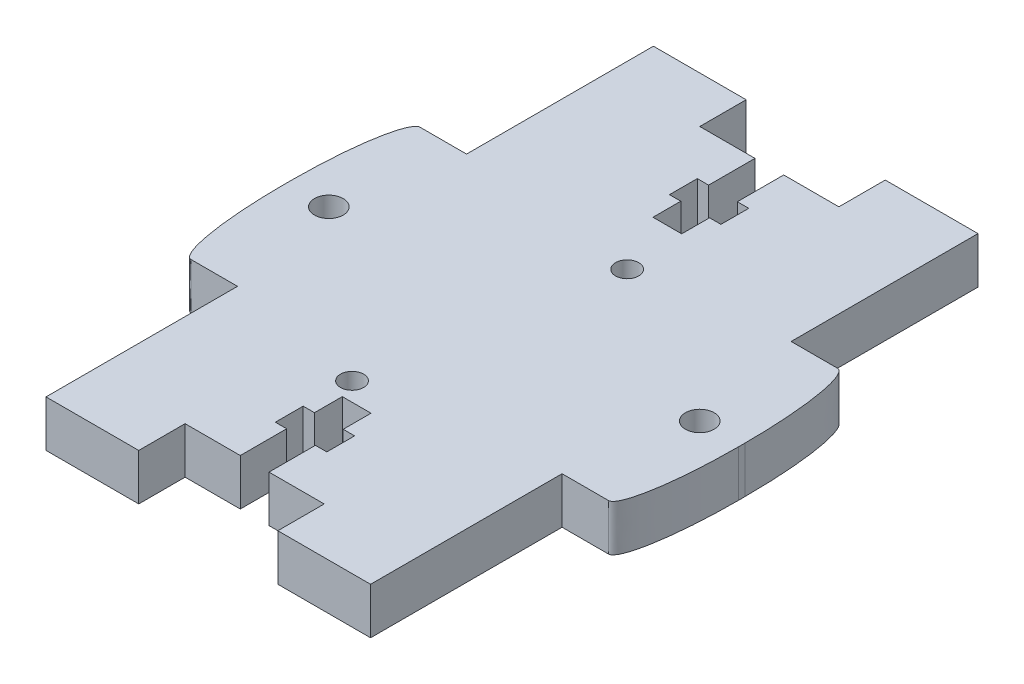
SolidWorks part; units mm, degrees
ref_plane "Plan de face" through (0, 0, 0) normal (0, 0, 1) x (1, 0, 0)
ref_plane "Plan de dessus" through (0, 0, 0) normal (0, 1, 0) x (1, 0, 0)
ref_plane "Plan de droite" through (0, 0, 0) normal (1, 0, 0) x (0, 0, -1)
ref_plane "Plan1" through (0, -5, 0) normal (0, -1, 0) x (1, 0, 0)
sketch "Esquisse1" plane through (0, -5, 0) normal (0, -1, 0) x (1, 0, 0)
  line L0 (17.5, 13.55) -> (17.5, 22.5)
  line L1 (17.5, 22.5) -> (-17.5, 22.5)
  line L2 (-17.5, 22.5) -> (-17.5, 13.55)
  line L3 (-17.5, 12.35) -> (-19.5485, 12.35)
  line L4 (-19.5485, 12.35) -> (-22.1586, 14.9601)
  line L5 (-22.5, 14.8186) -> (-22.5, -14.8186)
  line L6 (-22.1586, -14.9601) -> (-19.5485, -12.35)
  line L7 (-19.5485, -12.35) -> (-17.5, -12.35)
  line L8 (-17.5, -13.55) -> (-17.5, -30)
  line L9 (-17.5, -30) -> (17.5, -30)
  line L10 (17.5, -30) -> (17.5, -13.55)
  line L11 (17.5, -12.35) -> (19.5485, -12.35)
  line L12 (19.5485, -12.35) -> (22.1586, -14.9601)
  line L13 (22.5, -14.8186) -> (22.5, 14.8186)
  line L14 (22.1586, 14.9601) -> (19.5485, 12.35)
  line L15 (19.5485, 12.35) -> (17.5, 12.35)
  arc A0 (-17.5, 13.55) -> (-17.5, 12.35) centre (-17.5, 12.95) cw
  arc A1 (-22.1586, 14.9601) -> (-22.5, 14.8186) centre (-22.3, 14.8186) ccw
  arc A2 (-22.5, -14.8186) -> (-22.1586, -14.9601) centre (-22.3, -14.8186) ccw
  arc A3 (-17.5, -12.35) -> (-17.5, -13.55) centre (-17.5, -12.95) cw
  arc A4 (17.5, -13.55) -> (17.5, -12.35) centre (17.5, -12.95) cw
  arc A5 (22.1586, -14.9601) -> (22.5, -14.8186) centre (22.3, -14.8186) ccw
  arc A6 (22.5, 14.8186) -> (22.1586, 14.9601) centre (22.3, 14.8186) ccw
  arc A7 (17.5, 12.35) -> (17.5, 13.55) centre (17.5, 12.95) cw
extrude "Boss.-Extru.1" add sketch "Esquisse1" against normal blind 5
sketch "Esquisse2" plane through (0, 0, 22.5) normal (0, 0, 1) x (1, 0, 0)
  line L0 (7.95, 0) -> (17.5, 0)
  line L1 (17.5, 0) -> (17.5, -5)
  line L2 (17.5, -5) -> (5, -5)
  line L3 (5, -5) -> (5, -2.95)
  line L4 (5, -2.95) -> (7.95, 0)
extrude "Boss.-Extru.2" add sketch "Esquisse2" along normal blind 8
sketch "Esquisse3" plane through (0, 0, 22.5) normal (0, 0, 1) x (1, 0, 0)
  line L0 (-7.95, 0) -> (-5, -2.95)
  line L1 (-5, -2.95) -> (-5, -5)
  line L2 (-5, -5) -> (-17.5, -5)
  line L3 (-17.5, -5) -> (-17.5, 0)
  line L4 (-17.5, 0) -> (-7.95, 0)
extrude "Boss.-Extru.3" add sketch "Esquisse3" along normal blind 8
fillet "Congé1" radius 1.6 6 edges at (-19.5485, -2.5, 12.35) (19.5485, -2.5, -12.35) (-19.5485, -2.5, -12.35) (5, -2.95, 26.5) (19.5485, -2.5, 12.35) (-5, -2.95, 26.5) tangent propagation no
sketch "Esquisse8" plane through (0, 0, 0) normal (0, 1, 0) x (1, 0, 0)
  line L0 (-17.5, 30) -> (17.5, 30) construction
  line L1 (7.95, -30.5) -> (-7.95, -30.5)
  line L2 (7.95, -30.5) -> (7.95, -22.5)
  line L3 (7.95, -22.5) -> (-7.95, -22.5)
  line L4 (-7.95, -30.5) -> (-7.95, -22.5)
  line L5 (-5.6722, -16.5859) -> (-12.1608, -16.5859)
  line L6 (-5.6722, -16.5859) -> (-5.6722, -5.1949)
  line L7 (-5.6722, -5.1949) -> (-12.1608, -5.1949)
  line L8 (-12.1608, -16.5859) -> (-12.1608, -5.1949)
  line L9 (5.142, 7.638) -> (-5.6722, 7.638)
  line L10 (5.142, 7.638) -> (5.142, 30)
  line L11 (5.142, 30) -> (-5.6722, 30)
  line L12 (-5.6722, 7.638) -> (-5.6722, 30)
  line L13 (17.5, -13.55) -> (17.5, -30.5) construction
  line L14 (17.5, -16.5859) -> (15.5476, -16.5859)
  line L15 (17.5, -16.5859) -> (17.5, 15.4001)
  line L16 (17.5, 15.4001) -> (15.5476, 15.4001)
  line L17 (15.5476, -16.5859) -> (15.5476, 15.4001)
  line L18 (-17.5, -30.5) -> (-17.5, -13.55) construction
  line L19 (-17.5, -15.9862) -> (-14.5166, -15.9862)
  line L20 (-17.5, -15.9862) -> (-17.5, 14.9403)
  line L21 (-17.5, 14.9403) -> (-14.5166, 14.9403)
  line L22 (-14.5166, -15.9862) -> (-14.5166, 14.9403)
  line L23 (17.5, 12.35) -> (18.8858, 12.35) construction
  line L24 (-17.5, -12.35) -> (-24.5, -12.35)
  line L25 (-17.5, -12.35) -> (-17.5, 12.35)
  line L26 (-17.5, 12.35) -> (-24.5, 12.35)
  line L27 (-24.5, -12.35) -> (-24.5, 12.35)
  line L28 (17.5, -12.35) -> (24.5, -12.35)
  line L29 (17.5, -12.35) -> (17.5, 12.35)
  line L30 (17.5, 12.35) -> (24.5, 12.35)
  line L31 (24.5, -12.35) -> (24.5, 12.35)
  line L32 (-18.8858, 12.35) -> (-17.5, 12.35) construction
  line L33 (-22.5, -14.8186) -> (-22.5, 14.8186) construction
  line L34 (22.5, 14.8186) -> (22.5, -14.8186) construction
  arc M5 (17.5, -13.55) -> (17.5, -12.35) centre (17.5, -12.95) cw
  line M10 (22.5, -14.8186) -> (22.5, 14.8186)
  arc M15 (17.5, 12.35) -> (17.5, 13.55) centre (17.5, 12.95) cw
  arc M19 (-17.5, 13.55) -> (-17.5, 12.35) centre (-17.5, 12.95) cw
  line M24 (-22.5, 14.8186) -> (-22.5, -14.8186)
  arc M29 (-17.5, -12.35) -> (-17.5, -13.55) centre (-17.5, -12.95) cw
  line M32 (-7.95, -30.5) -> (-7.95, -22.5)
  line M33 (-7.95, -22.5) -> (7.95, -22.5)
  line M34 (7.95, -22.5) -> (7.95, -30.5)
  dimension "D1" = 0
  dimension "D2" = 0
  dimension "D3" = 2
  dimension "D4" = 2
extrude "Boss.-Extru.4" add sketch "Esquisse8" against normal blind 5 contours L28 L31 L30 M10 | L15 M5 | L15 M15 | L1 M34 M33 M32 | L20 M29 | L27 L24 L26 M24 | L20 M19 region at (0, 0, 26.5) region at (17.2454, 0, 12.95) region at (17.2454, 0, -12.95) region at (23.5, 0, 0) region at (-17.2454, 0, 12.95) region at (-17.2454, 0, -12.95) region at (-23.5, 0, 0)
sketch "Esquisse9" plane through (0, 0, 0) normal (0, 1, 0) x (1, 0, 0)
  line L0 (18.8858, -12.35) -> (17.5, -12.35) construction
  line L1 (18.1929, -12.35) -> (26.3546, -12.35)
  line L2 (18.1929, -12.35) -> (18.1929, -16.2736)
  line L3 (18.1929, -16.2736) -> (26.3546, -16.2736)
  line L4 (26.3546, -12.35) -> (26.3546, -16.2736)
  line L5 (17.5, 12.35) -> (18.8858, 12.35) construction
  line L6 (18.8858, 12.35) -> (24.8026, 12.35)
  line L7 (18.8858, 12.35) -> (18.8858, 17.5845)
  line L8 (18.8858, 17.5845) -> (24.8026, 17.5845)
  line L9 (24.8026, 12.35) -> (24.8026, 17.5845)
  line L10 (-18.8858, 12.35) -> (-17.5, 12.35) construction
  line L11 (-18.1929, 12.35) -> (-25.3236, 12.35)
  line L12 (-18.1929, 12.35) -> (-18.1929, 16.4348)
  line L13 (-18.1929, 16.4348) -> (-25.3236, 16.4348)
  line L14 (-25.3236, 12.35) -> (-25.3236, 16.4348)
  line L15 (-17.5, -12.35) -> (-18.8858, -12.35) construction
  line L16 (-18.1929, -12.35) -> (-23.1392, -12.35)
  line L17 (-18.1929, -12.35) -> (-18.1929, -15.4688)
  line L18 (-18.1929, -15.4688) -> (-23.1392, -15.4688)
  line L19 (-23.1392, -12.35) -> (-23.1392, -15.4688)
  line L20 (-17.5, -30.5) -> (-17.5, -12.35) construction
  line L21 (17.5, -30.5) -> (-17.5, -30.5)
  line L22 (17.5, -30.5) -> (17.5, -28)
  line L23 (17.5, -28) -> (-17.5, -28)
  line L24 (-17.5, -30.5) -> (-17.5, -28)
  line L25 (-17.5, 12.35) -> (-17.5, 30) construction
  line L26 (17.5, 30) -> (-17.5, 30)
  line L27 (17.5, 30) -> (17.5, 27.5)
  line L28 (17.5, 27.5) -> (-17.5, 27.5)
  line L29 (-17.5, 30) -> (-17.5, 27.5)
  arc A0 (18.8858, 12.35) -> (20.0172, 12.8186) centre (18.8858, 13.95) ccw construction
  dimension "D1" = 2.5
  dimension "D2" = 2.5
extrude "Enlèv. mat.-Extru.1" cut sketch "Esquisse9" against normal through all
sketch "Esquisse10" plane through (0, 0, 0) normal (0, 1, 0) x (1, 0, 0)
  line L0 (1.55, -28) -> (-1.55, -28)
  line L1 (1.55, -28) -> (1.55, -17)
  line L2 (1.55, -17) -> (-1.55, -17)
  line L3 (-1.55, -28) -> (-1.55, -17)
  line L4 (2.78, -23) -> (-2.77, -23)
  line L5 (2.78, -23) -> (2.78, -20)
  line L6 (2.78, -20) -> (-2.77, -20)
  line L7 (-2.77, -23) -> (-2.77, -20)
  line L8 (1.55, 16.5) -> (-1.55, 16.5)
  line L9 (1.55, 16.5) -> (1.55, 27.5)
  line L10 (1.55, 27.5) -> (-1.55, 27.5)
  line L11 (-1.55, 16.5) -> (-1.55, 27.5)
  line L12 (2.78, 19.5) -> (-2.77, 19.5)
  line L13 (2.78, 19.5) -> (2.78, 22.5)
  line L14 (2.78, 22.5) -> (-2.77, 22.5)
  line L15 (-2.77, 19.5) -> (-2.77, 22.5)
  line L17 (17.5, -12.35) -> (17.5, -28) construction
  line L19 (17.5, 27.5) -> (17.5, 12.35) construction
  line L20 (17.5, -28) -> (-17.5, -28) construction
  line L21 (-17.5, 27.5) -> (17.5, 27.5) construction
  dimension "D1" = 3
  dimension "D2" = 3
  dimension "D3" = 5.55
  dimension "D4" = 3.1
  dimension "D5" = 1.23
  dimension "D6" = 3
  dimension "D7" = 5
  dimension "D8" = 5.55
  dimension "D9" = 3.1
  dimension "D10" = 1.23
  dimension "D11" = 0
  dimension "D12" = 11
  dimension "D13" = 15.95
  dimension "D14" = 11
  dimension "D15" = 0
  dimension "D16" = 15.95
extrude "Enlèv. mat.-Extru.2" cut sketch "Esquisse10" against normal through all contours L1 L4 L3 | L1 L6 L3 L4 | L5 L6 L1 L4 | L6 L1 L2 L3 | L7 L4 L3 L6 | L9 L12 L11 L8 | L13 L14 L9 L12 | L9 L14 L11 L12 | L15 L12 L11 L14 | L14 L9 L11 region at (0, 0, 25.5) region at (0, 0, 21.5) region at (2.165, 0, 21.5) region at (-2.16, 0, 21.5) region at (0, 0, 18.5) region at (0, 0, -18) region at (0, 0, -21) region at (2.165, 0, -21) region at (-2.16, 0, -21) region at (0, 0, -25)
sketch "Esquisse11" plane through (0, 0, 0) normal (0, 1, 0) x (1, 0, 0)
  line L0 (-17.5, -28) -> (-17.5, -12.35) construction
  line L2 (-1.55, -28) -> (-17.5, -28) construction
  circle A0 centre (-2.5, -15) radius 1.25
  circle A1 centre (1.9196, 10.2476) radius 1.25
  dimension "D1" = 2.5
  dimension "D2" = 15
  dimension "D3" = 4.4196
  dimension "D4" = 2.5
  dimension "D5" = 25.2476
  dimension "D6" = 13
extrude "Enlèv. mat.-Extru.3" cut sketch "Esquisse11" against normal through all
sketch "Esquisse12" plane through (0, 0, 0) normal (0, 1, 0) x (1, 0, 0)
  line L0 (-17.5, -28) -> (-17.5, -12.35) construction
  line L1 (17.5, -12.35) -> (17.5, -28) construction
  line L3 (24.5, -12.35) -> (17.5, -12.35) construction
  line L4 (-17.5, -12.35) -> (-24.5, -12.35) construction
  circle A0 centre (20, 0) radius 1.55
  circle A1 centre (-20, 0) radius 1.55
  dimension "D1" = 3.1
  dimension "D2" = 3.1
  dimension "D3" = 2.5
  dimension "D4" = 2.5
  dimension "D5" = 12.35
  dimension "D6" = 12.35
extrude "Enlèv. mat.-Extru.4" cut sketch "Esquisse12" against normal through all
fillet "Congé2" radius 12 2 edges at (-24.5, -2.5, -12.35) (24.5, -2.5, 12.35) second distance 2 first distance on face at (-24.5, -2.5, 0) first distance on face at (24.5, -2.5, 0)
fillet "Congé3" radius 12 1 edges at (-24.5, -2.5, 12.35) second distance 2 first distance on face at (-24.5, -1.875, 9.175)
fillet "Congé4" radius 12 1 edges at (24.5, -2.5, -12.35) second distance 2 first distance on face at (24.5, -1.875, -2.825)
sketch "Esquisse13" plane through (0, 0, 0) normal (0, 1, 0) x (1, 0, 0)
  line L0 (0, 0) -> (0, -11.5199) construction
  line L1 (17.5, -28) -> (7.5, -28)
  line L2 (17.5, -28) -> (17.5, -33)
  line L3 (17.5, -33) -> (7.5, -33)
  line L4 (7.5, -28) -> (7.5, -33)
  line L5 (-4.2209, -0.25) -> (-15.5238, -0.25) construction
  line L6 (-7.5, -28) -> (-7.5, -33)
  line L7 (-17.5, -33) -> (-7.5, -33)
  line L8 (-17.5, -28) -> (-17.5, -33)
  line L9 (-17.5, -28) -> (-7.5, -28)
  line L11 (-17.5, 27.5) -> (-7.5, 27.5)
  line L12 (-17.5, 27.5) -> (-17.5, 32.5)
  line L13 (-17.5, 32.5) -> (-7.5, 32.5)
  line L14 (-7.5, 27.5) -> (-7.5, 32.5)
  line L15 (7.5, 27.5) -> (7.5, 32.5)
  line L16 (17.5, 32.5) -> (7.5, 32.5)
  line L17 (17.5, 27.5) -> (17.5, 32.5)
  line L18 (17.5, 27.5) -> (7.5, 27.5)
  dimension "D1" = 5
  dimension "D2" = 10
  dimension "D3" = 27.75
extrude "Boss.-Extru.5" add sketch "Esquisse13" against normal up to surface (5 mm away) up to face at (20, -5, 1.55)
